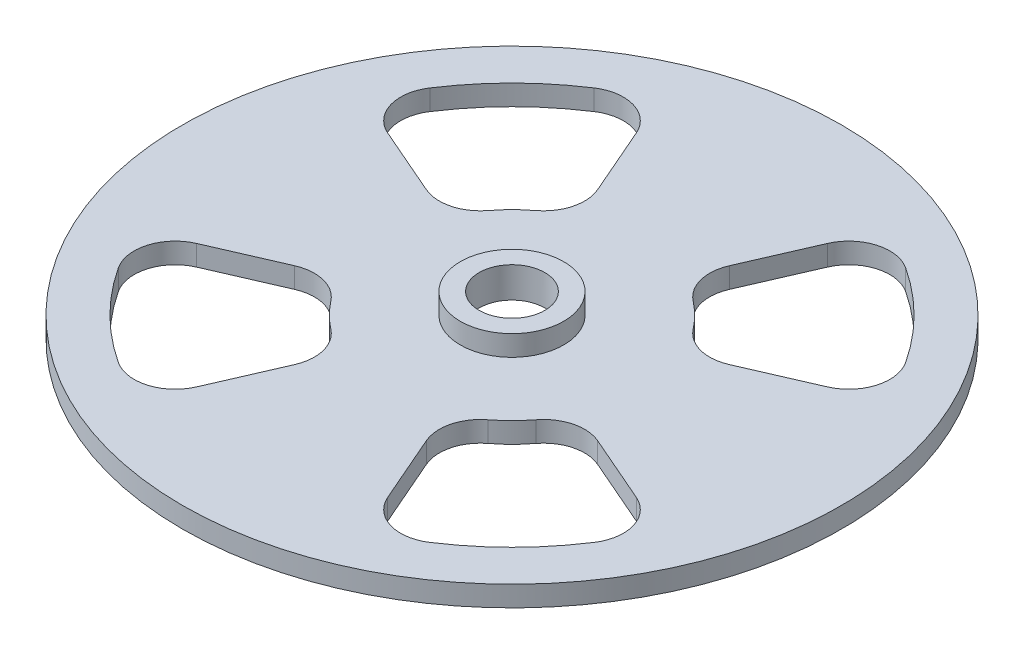
SolidWorks part; units mm, degrees
ref_plane "Front Plane" through (0, 0, 0) normal (0, 0, 1) x (1, 0, 0)
ref_plane "Top Plane" through (0, 0, 0) normal (0, 1, 0) x (1, 0, 0)
ref_plane "Right Plane" through (0, 0, 0) normal (1, 0, 0) x (0, 0, -1)
sketch "Sketch1" plane through (0, 0, 0) normal (0, 1, 0) x (1, 0, 0)
  circle A0 centre (0, 0) radius 25.5
  dimension "D1" = 51
extrude "Boss-Extrude1" add sketch "Sketch1" along normal blind 1.5875 contours A0 region at (0, 0, 0)
sketch "Sketch2" plane through (0, 1.5875, 0) normal (0, 1, 0) x (1, 0, 0)
  line L0 (0, 0) -> (0, 25.5) construction
  line L1 (0, 0) -> (25.5, 0) construction
  line L2 (5.0987, 11.7262) -> (7.3989, 17.0163)
  line L3 (11.7262, 5.0987) -> (17.0163, 7.3989)
  line L4 (5.0987, 11.7262) -> (0, 11.7262) construction
  line L5 (11.7262, 5.0987) -> (11.7262, 0) construction
  line L6 (-11.7262, 5.0987) -> (-17.0163, 7.3989)
  line L7 (-5.0987, 11.7262) -> (-7.3989, 17.0163)
  line L8 (-11.7262, -5.0987) -> (-17.0163, -7.3989)
  line L9 (-5.0987, -11.7262) -> (-7.3989, -17.0163)
  line L10 (11.7262, -5.0987) -> (17.0163, -7.3989)
  line L11 (5.0987, -11.7262) -> (7.3989, -17.0163)
  arc A1 (7.9394, 6.08) -> (6.08, 7.9394) centre (0, 0) ccw
  arc A2 (12.0496, 18.4067) -> (18.4067, 12.0496) centre (0, 0) cw
  arc A3 (7.9394, 6.08) -> (11.7262, 5.0987) centre (10.4602, 8.0104) ccw
  arc A4 (18.4067, 12.0496) -> (17.0163, 7.3989) centre (15.7503, 10.3106) cw
  arc A5 (12.0496, 18.4067) -> (7.3989, 17.0163) centre (10.3106, 15.7503) ccw
  arc A6 (6.08, 7.9394) -> (5.0987, 11.7262) centre (8.0104, 10.4602) cw
  arc A7 (-6.08, 7.9394) -> (-5.0987, 11.7262) centre (-8.0104, 10.4602) ccw
  arc A8 (-7.9394, 6.08) -> (-6.08, 7.9394) centre (0, 0) cw
  arc A9 (-7.9394, 6.08) -> (-11.7262, 5.0987) centre (-10.4602, 8.0104) cw
  arc A10 (-18.4067, 12.0496) -> (-17.0163, 7.3989) centre (-15.7503, 10.3106) ccw
  arc A11 (-12.0496, 18.4067) -> (-18.4067, 12.0496) centre (0, 0) ccw
  arc A12 (-12.0496, 18.4067) -> (-7.3989, 17.0163) centre (-10.3106, 15.7503) cw
  arc A13 (-7.9394, -6.08) -> (-6.08, -7.9394) centre (0, 0) ccw
  arc A14 (-7.9394, -6.08) -> (-11.7262, -5.0987) centre (-10.4602, -8.0104) ccw
  arc A15 (-18.4067, -12.0496) -> (-17.0163, -7.3989) centre (-15.7503, -10.3106) cw
  arc A16 (-12.0496, -18.4067) -> (-18.4067, -12.0496) centre (0, 0) cw
  arc A17 (-12.0496, -18.4067) -> (-7.3989, -17.0163) centre (-10.3106, -15.7503) ccw
  arc A18 (-6.08, -7.9394) -> (-5.0987, -11.7262) centre (-8.0104, -10.4602) cw
  arc A19 (7.9394, -6.08) -> (6.08, -7.9394) centre (0, 0) cw
  arc A20 (7.9394, -6.08) -> (11.7262, -5.0987) centre (10.4602, -8.0104) cw
  arc A21 (18.4067, -12.0496) -> (17.0163, -7.3989) centre (15.7503, -10.3106) ccw
  arc A22 (12.0496, -18.4067) -> (18.4067, -12.0496) centre (0, 0) ccw
  arc A23 (12.0496, -18.4067) -> (7.3989, -17.0163) centre (10.3106, -15.7503) cw
  arc A24 (6.08, -7.9394) -> (5.0987, -11.7262) centre (8.0104, -10.4602) ccw
  circle A25 centre (0, 0) radius 25.5 construction
  dimension "D1" = 10
  dimension "D2" = 3.175
  dimension "D3" = 22
  dimension "D4" = 43
extrude "Cut-Extrude1" cut sketch "Sketch2" against normal up to next
sketch "Sketch3" plane through (0, 1.5875, 0) normal (0, 1, 0) x (1, 0, 0)
  circle A0 centre (0, 0) radius 4
  circle A1 centre (0, 0) radius 25.5 construction
  dimension "D1" = 8
extrude "Boss-Extrude2" add sketch "Sketch3" along normal blind 1.5875
sketch "Sketch4" plane through (0, 3.175, 0) normal (0, 1, 0) x (1, 0, 0)
  circle A0 centre (0, 0) radius 2.54
  dimension "D1" = 5.08
extrude "Cut-Extrude2" cut sketch "Sketch4" against normal up to next
sketch "Sketch5" plane through (0, 0, 0) normal (0, -1, 0) x (1, 0, 0)
  circle A0 centre (0, 0) radius 6
  dimension "D1" = 12
extrude "Cut-Extrude3" cut sketch "Sketch5" against normal blind 0.8
